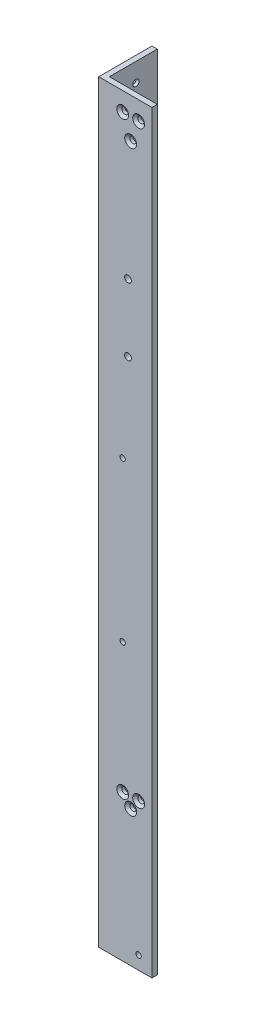
SolidWorks part; units mm, degrees
ref_plane "Front Plane" through (0, 0, 0) normal (0, 0, 1) x (1, 0, 0)
ref_plane "Top Plane" through (0, 0, 0) normal (0, 1, 0) x (1, 0, 0)
ref_plane "Right Plane" through (0, 0, 0) normal (1, 0, 0) x (0, 0, -1)
sketch "Sketch2" plane through (0, 0, 0) normal (0, 1, 0) x (1, 0, 0)
  line L0 (0, 31.75) -> (3.175, 31.75)
  line L1 (3.175, 31.75) -> (3.175, 3.175)
  line L2 (3.175, 3.175) -> (31.75, 3.175)
  line L3 (31.75, 3.175) -> (31.75, 0)
  line L4 (31.75, 0) -> (0, 0)
  line L5 (0, 0) -> (0, 31.75)
  point P9 (1.5875, 31.75)
  point P10 (31.75, 1.5875)
  dimension "D4" = 3.175
  dimension "D1" = 31.75
  dimension "D2" = 31.75
  dimension "D3" = 3.175
extrude "Boss-Extrude1" add sketch "Sketch2" along normal blind 450
sketch "FrontSideHoles-Sketch3" plane through (0, 0, 0) normal (0, 0, 1) x (1, 0, 0)
  line L0 (0, 0) -> (31.75, 0) construction
  line L1 (0, 450) -> (0, 0) construction
  circle A1 centre (19.05, 81.1125) radius 1.5875
  circle A2 centre (14.2875, 87.4625) radius 1.5875
  circle A3 centre (23.8125, 87.4625) radius 1.5875
  circle A4 centre (14.2875, 438.8875) radius 1.5875
  circle A6 centre (23.8125, 438.8875) radius 1.5875
  circle A7 centre (19.05, 426.1875) radius 1.5875
  circle A8 centre (17.4625, 354.1849) radius 2
  circle A9 centre (17.4625, 313.9849) radius 2
  circle A10 centre (14.2875, 260) radius 1.5875
  circle A11 centre (14.2875, 165) radius 1.5875
  circle A14 centre (23.8125, 7.9375) radius 1.5875
  dimension "D4" = 3.175
  dimension "D15" = 4
  dimension "D13" = 3.175
  dimension "D8" = 11.1125
  dimension "D11" = 40.2
  dimension "D6" = 165
  dimension "D10" = 95
  dimension "D2" = 14.2875
  dimension "D5" = 6.35
  dimension "D14" = 81.1125
  dimension "D7" = 12.7
  dimension "D16" = 17.4625
  dimension "D9" = 354.1849
  dimension "D17" = 19.05
  dimension "D3" = 23.8125
  dimension "D12" = 7.9375
sketch "LeftSideHoles-Sketch4" plane through (0, 0, 0) normal (-1, 0, 0) x (0, 0, 1)
  line L0 (-31.75, 450) -> (0, 450) construction
  line L1 (0, 450) -> (0, 0) construction
  line L3 (-31.75, 0) -> (0, 0) construction
  circle A0 centre (-23.8125, 81.1125) radius 1.5875
  circle A1 centre (-14.2875, 81.1125) radius 1.5875
  circle A2 centre (-19.05, 87.4625) radius 1.5875
  circle A4 centre (-19.05, 438.8875) radius 1.5875
  circle A6 centre (-23.8125, 426.1875) radius 1.5875
  circle A7 centre (-14.2875, 426.1875) radius 1.5875
  circle A8 centre (-23.8125, 341.2474) radius 1.5875
  circle A9 centre (-14.2875, 341.2474) radius 1.5875
  circle A10 centre (-23.8125, 306.3224) radius 1.5875
  circle A11 centre (-14.2875, 306.3224) radius 1.5875
  circle A12 centre (-23.8125, 7.9375) radius 1.5875
  circle A14 centre (-14.2875, 165) radius 1.5875
  circle A15 centre (-14.2875, 260) radius 1.5875
  circle A16 centre (-14.2875, 355) radius 1.5875
  dimension "D4" = 3.175
  dimension "D2" = 14.2875
  dimension "D5" = 6.35
  dimension "D7" = 12.7
  dimension "D3" = 81.1125
  dimension "D6" = 11.1125
  dimension "D10" = 7.9375
  dimension "D9" = 34.925
  dimension "D8" = 341.2474
  dimension "D12" = 165
  dimension "D13" = 95
  dimension "D14" = 95
  dimension "D15" = 19.05
  dimension "D11" = 23.8125
extrude "FrontSideHoles-Cut-Extrude1" cut sketch "FrontSideHoles-Sketch3" against normal blind 3.175
extrude "LeftSideHoles-Cut-Extrude2" cut sketch "LeftSideHoles-Sketch4" against normal blind 3.175
sketch "Sketch3" plane through (0, 0, 0) normal (0, 0, 1) x (1, 0, 0)
  point P0 (14.2875, 87.4625)
  point P3 (19.05, 81.1125)
  point P6 (23.8125, 87.4625)
  point P9 (19.05, 426.1875)
  point P12 (14.2875, 438.8875)
  point P15 (23.8125, 438.8875)
hole_wizard "CSK for #6 Flat Head Machine Screw (100)1" positions "Sketch3" profile "Sketch4" countersink size "#6" standard "ANSI Inch" end condition through all
sketch "Sketch4" plane through (14.2875, 87.4625, 0) normal (1, 0, 0) x (0, -1, 0)
  line L0 (0, 0) -> (0, 31.75)
  line L1 (0, 31.75) -> (1.8986, 31.75)
  line L2 (1.8986, 31.75) -> (1.8986, 1.38)
  line L3 (1.8986, 1.38) -> (3.5433, 0)
  line L5 (3.5433, 0) -> (0, 0)
  line L6 (-1.8986, 1.38) -> (-3.5433, 0) construction
  line L11 (0, -6.35) -> (0, 107.95) construction
  dimension "Thru Hole Dia." = 3.7973
  dimension "Thru Hole Depth" = 31.75
  dimension "Near C'Sink Dia." = 7.0866
  dimension "Near C'Sink Angle" = 100
sketch "Sketch8" plane through (0, 0, 0) normal (-1, 0, 0) x (0, 0, 1)
  point P0 (-19.05, 87.4625)
  point P3 (-23.8125, 81.1125)
  point P6 (-14.2875, 81.1125)
  point P9 (-23.8125, 341.2474)
  point P12 (-14.2875, 341.2474)
  point P15 (-14.2875, 306.3224)
  point P18 (-23.8125, 306.3224)
  point P21 (-23.8125, 426.1875)
  point P24 (-14.2875, 426.1875)
  point P27 (-19.05, 438.8875)
hole_wizard "CSK for #6 Flat Head Machine Screw (100)2" positions "Sketch8" profile "Sketch9" countersink size "#6" standard "ANSI Inch" end condition through all
sketch "Sketch9" plane through (0, 87.4625, -19.05) normal (0, 1, 0) x (0, 0, 1)
  line L0 (0, 0) -> (0, 31.75)
  line L1 (0, 31.75) -> (1.8986, 31.75)
  line L2 (1.8986, 31.75) -> (1.8986, 1.38)
  line L3 (1.8986, 1.38) -> (3.5433, 0)
  line L5 (3.5433, 0) -> (0, 0)
  line L6 (-1.8986, 1.38) -> (-3.5433, 0) construction
  line L11 (0, -6.35) -> (0, 107.95) construction
  dimension "Thru Hole Dia." = 3.7973
  dimension "Thru Hole Depth" = 31.75
  dimension "Near C'Sink Dia." = 7.0866
  dimension "Near C'Sink Angle" = 100
equation "\"RailThickness\"= .125in'Spec"
equation "\"VSWidth\"= 1.25in'Spec"
equation "\"VSHeight\"= 1.25in'Spec"
equation "\"VSLength\"= 450mm"
equation "\"HoleOffsetFromEdge\"= \"RailThickness\" * 2.5"
equation "\"HoleOffsetFromSide\"= \"RailThickness\" * 3.5"
equation "\"LegHeight\"= 70mm'Space needed for PSU/Stepper/Electronics"
equation "\"VSBottomSideRailHoleY1FromBottomOfLowerRail\"= \"V1 BottomOfLowerRail\" + \"HoleOffsetFromSide\"'Equals 81.1125"
equation "\"VSSideRailHoleX1FromSide\"= \"HoleOffsetFromSide\" + \"RailThickness\""
equation "\"FasteningHoleDiameter\"= .125in"
equation "\"VSBottomSideRailHoleY2FromY1\"= \"LowerRailHeight\" - \"HoleOffsetFromSide\" - \"HoleOffsetFromEdge\"'Equals 6.35"
equation "\"VSTopSideRailHoleY1FromEdge\"= \"HoleOffsetFromEdge\" + \"RailThickness\""
equation "\"D4@FrontSideHoles-Sketch3\" = \"FasteningHoleDiameter\""
equation "\"D1@Boss-Extrude1\"=\"VSLength\""
equation "\"D4@LeftSideHoles-Sketch4\" = \"FasteningHoleDiameter\""
equation "\"D3@LeftSideHoles-Sketch4\"= \"VSBottomSideRailHoleY1FromBottomOfLowerRail\""
equation "\"D8@FrontSideHoles-Sketch3\" = \"VSTopSideRailHoleY1FromEdge\""
equation "\"D6@LeftSideHoles-Sketch4\" = \"VSTopSideRailHoleY1FromEdge\""
equation "\"VSMidSideRailHoleY1FromV8TopOfMidSideRail\"= \"V8 ToTopOfMidSideRail\" - \"HoleOffsetFromEdge\"'Equals 341.24737"
equation "\"LowerRailHeight\"= 1.00in"
equation "\"D1@Sketch2\"=\"VSHeight\""
equation "\"D2@Sketch2\"=\"VSWidth\""
equation "\"TopRailHeight\"= 1.25in"
equation "\"MidLeftOrRightSideRailHeight\"= 2.0in"
equation "\"D10@LeftSideHoles-Sketch4\"=\"HoleOffsetFromEdge\""
equation "\"VSMidSideRailHoleY2FromY1\"= \"MidLeftOrRightSideRailHeight\" - \"HoleOffsetFromEdge\" * 2'Equals 34.925"
equation "\"D9@LeftSideHoles-Sketch4\"=\"VSMidSideRailHoleY2FromY1\""
equation "\"VSSideRailHoleX2FromSide\"= \"VSWidth\" - \"HoleOffsetFromEdge\""
equation "\"VSTopSideRailHoleY2FromY1\"= \"TopRailHeight\" - \"VSTopSideRailHoleY1FromEdge\" - \"HoleOffsetFromEdge\"'Equals 12.7"
equation "\"D7@LeftSideHoles-Sketch4\"=\"VSTopSideRailHoleY2FromY1\""
equation "\"BeltTensionerInnerHeight\"= \"20TGT2PulleyWidth\" * 2 + \"1mmSpacer\" * 3"
equation "\"20TGT2PulleyWidth\"= 8.7mm'The STL of the Pulley in the diagram is a bit larger"
equation "\"1mmSpacer\"= 1mm"
equation "\"BeltTensionerHeight\"= 60mm"
equation "\"D11@FrontSideHoles-Sketch3\"=\"VSBeltTensionerHoleY2FromY1\""
equation "\"VSBeltTensionerHoleY1ToAlignWithYAxisGantryBlockUpperPulley\"= \"V5 ToBottomOfXAxisLinearRail\" - \"DistanceFromXAxisLinearRailBottomAndTopGantryPulley\" + \"DistanceFromBeltTensionerTopPulleyToBeltTensionertop\" - \"BeltTensionerMountingHoleOffsetFromTopOrBottom\"'Equals 354.18487"
equation "\"VSBeltTensionerHoleY2FromY1\"= \"BeltTensionerHeight\" - \"BeltTensionerMountingHoleOffsetFromTopOrBottom\" * 2"
equation "\"V1 BottomOfLowerRail\"= \"LegHeight\""
equation "\"StepperShaftLength\"= 24mm'Pulley will be attached to the end"
equation "\"ZAxisLeadScrewLength\"= 200mm"
equation "\"LM8UUHeight\"= 24mm'Spec"
equation "\"V2 ToBedAtTopOfZAxis\"= \"V1 BottomOfLowerRail\" - \"LowerEnclosureThickness\" + \"StepperShaftLength\" + \"ZAxisLeadScrewLength\" - \"LM8UUHeight\" / 2'Equals 277"
equation "\"HotEndToTopOfXAxisGB\"= 71.68487mm'Equals 71.68487. Measured after installed onto X-Axis linear rail guide block"
equation "\"TopOfGBToBottomOfLinearRail\"= \"LinearGBWidth\" / 2 + \"LinearRailWidth\" / 2'Equals 19.5"
equation "\"LinearGBWidth\"= 27mm'Spec"
equation "\"V5 ToBottomOfXAxisLinearRail\"= \"V4 ToTopOfBuildPlate/HotEndTip\" + \"HotEndToTopOfXAxisGB\" - \"TopOfGBToBottomOfLinearRail\"'Equals 352.18487"
equation "\"LinearRailWidth\"= 12mm'Spec"
equation "\"V6 ToMiddleOfYAxisGantryBlock\"= \"V5 ToBottomOfXAxisLinearRail\" - \"GABHeight\" / 2'Equals 334.18487"
equation "\"GABUpperHeight\"= 4mm"
equation "\"GABMidWallHeight\"= 28mm'Must equal 28 or changes alignment"
equation "\"D8@LeftSideHoles-Sketch4\"= \"VSMidSideRailHoleY1FromV8TopOfMidSideRail\""
equation "\"BedToBuildPlateStandoffLength\"= 15mm"
equation "\"BuildPlateHeight\"= 8mm'Spec"
equation "\"V4 ToTopOfBuildPlate/HotEndTip\"= \"V2 ToBedAtTopOfZAxis\" + \"BedToBuildPlateStandoffLength\" + \"BuildPlateHeight\""
equation "\"V8 ToTopOfMidSideRail\"= \"V6 ToMiddleOfYAxisGantryBlock\" + \"MidSideRailVerticalOffset\"'Equals 349.18487"
equation "\"VSEnclosureOffsets\"= ( \"VSLength\" - \"LegHeight\" ) / 4"
equation "\"D6@FrontSideHoles-Sketch3\"=\"LegHeight\" + \"VSEnclosureOffsets\""
equation "\"D10@FrontSideHoles-Sketch3\"=\"VSEnclosureOffsets\""
equation "\"D13@LeftSideHoles-Sketch4\"=\"VSEnclosureOffsets\""
equation "\"D12@LeftSideHoles-Sketch4\"=\"LegHeight\" + \"VSEnclosureOffsets\""
equation "\"D2@FrontSideHoles-Sketch3\"=\"VSSideRailHoleX1FromSide\""
equation "\"D5@FrontSideHoles-Sketch3\"=\"VSBottomSideRailHoleY2FromY1\""
equation "\"D14@FrontSideHoles-Sketch3\"=\"VSBottomSideRailHoleY1FromBottomOfLowerRail\""
equation "\"D7@FrontSideHoles-Sketch3\"=\"VSTopSideRailHoleY2FromY1\""
equation "\"D5@LeftSideHoles-Sketch4\"=\"VSBottomSideRailHoleY2FromY1\""
equation "\"BeltTensionerMountingHoleDiameter\"= 4.0mm"
equation "\"D15@FrontSideHoles-Sketch3\"=\"BeltTensionerMountingHoleDiameter\""
equation "\"LowerEnclosureThickness\"= 5mm"
equation "\"GABLowerHeight\"= 4mm"
equation "\"GABHeight\"= \"GABLowerHeight\" + \"GABMidWallHeight\" + \"GABUpperHeight\""
equation "\"D14@LeftSideHoles-Sketch4\"=\"VSEnclosureOffsets\""
equation "\"BeltTensionerMountingHoleOffsetFromTopOrBottom\"= ( \"BeltTensionerHeight\" - \"BeltTensionerInnerHeight\" ) / 4"
equation "\"D13@FrontSideHoles-Sketch3\"=\"FasteningHoleDiameter\""
equation "\"VSBeltTensionerXMountingHoleOffsetFromSide\" = \"BeltTensionerMountingHoleOffsetFromEdge\" + \"RailThickness\""
equation "\"BeltTensionerMountingHoleOffsetFromEdge\"= \"HoleOffsetFromEdge\" + \"RailThickness\" * 2"
equation "\"D16@FrontSideHoles-Sketch3\"=\"VSBeltTensionerXMountingHoleOffsetFromSide\""
equation "\"MidSideRailVerticalOffset\"= \"LinearRailWidth\" + 3mm'Allows space for RodStabilizer to attach to bottom of MidSideRail"
equation "\"GABRiserBossOffset\"= 0.4mm'Aligns Pulleys inside edges to be 2.5mm (.5mm apart top to bottom)"
equation "\"GABMidShortRiserHeight\"= \"GABMidWallHeight\" / 2 - \"20TGT2PulleyWidth\"'Equals 5.3"
equation "\"7mmx1mmSpacerHeight\"= 1mm"
equation "\"D9@FrontSideHoles-Sketch3\"=\"VSBeltTensionerHoleY1ToAlignWithYAxisGantryBlockUpperPulley\""
equation "\"DistanceFromXAxisLinearRailBottomAndTopGantryPulley\"= \"GABUpperHeight\" + \"GABMidShortRiserHeight\" - \"GABRiserBossOffset\"'Equals 8.9"
equation "\"DistanceFromBeltTensionerTopPulleyToBeltTensionertop\"= \"7mmx1mmSpacerHeight\" + \"BeltTensionerTopHeight\"'Equals 20.8"
equation "\"BeltTensionerTopHeight\"= ( \"BeltTensionerHeight\" - \"BeltTensionerInnerHeight\" ) / 2'Equals 19.8"
equation "\"VSMidSideRailHoleXFromSideToCenter\"= \"RailThickness\" * 6"
equation "\"D17@FrontSideHoles-Sketch3\"=\"VSMidSideRailHoleXFromSideToCenter\""
equation "\"D2@LeftSideHoles-Sketch4\"=\"VSSideRailHoleX1FromSide\""
equation "\"D3@FrontSideHoles-Sketch3\"=\"VSSideRailHoleX2FromSide\""
equation "\"D12@FrontSideHoles-Sketch3\"=\"HoleOffsetFromEdge\""
equation "\"D11@LeftSideHoles-Sketch4\"=\"VSSideRailHoleX2FromSide\""
equation "\"D15@LeftSideHoles-Sketch4\"=\"VSMidSideRailHoleXFromSideToCenter\""
